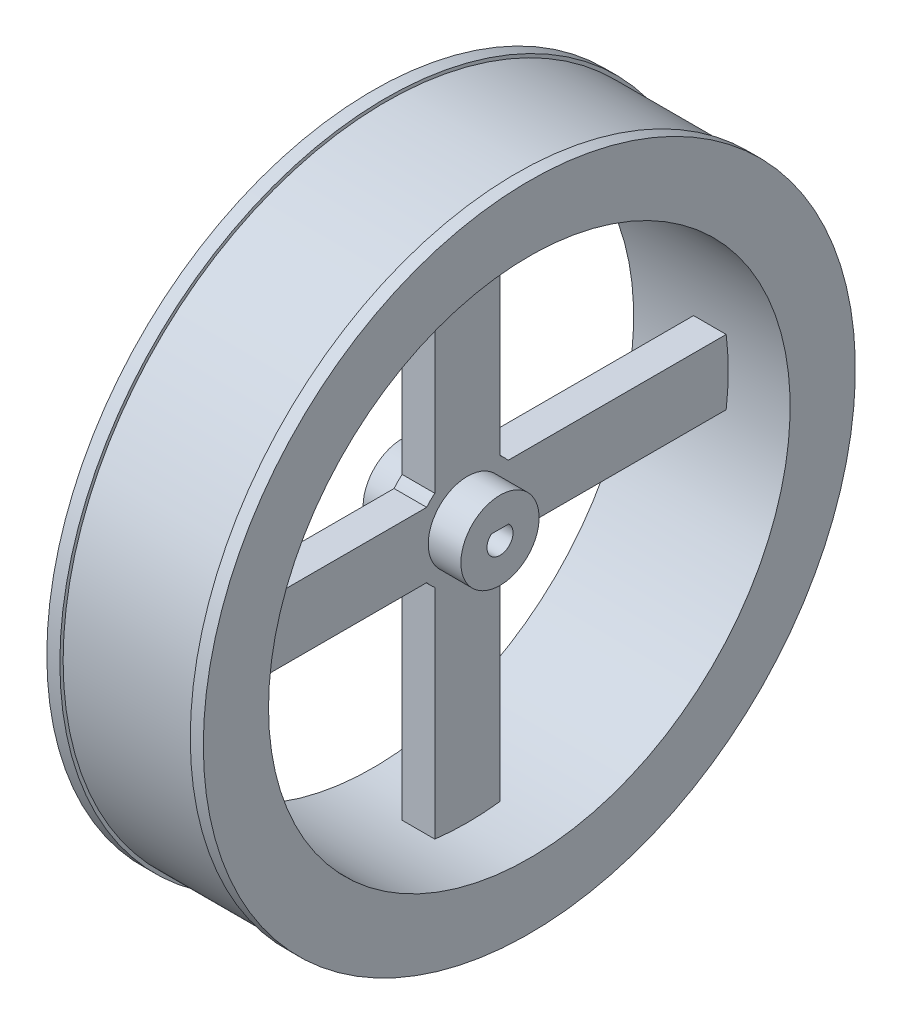
SolidWorks part; units mm, degrees
material "PLA (Black)"
ref_plane "Front Plane" through (0, 0, 0) normal (0, 0, 1) x (1, 0, 0)
ref_plane "Top Plane" through (0, 0, 0) normal (0, 1, 0) x (1, 0, 0)
ref_plane "Right Plane" through (0, 0, 0) normal (1, 0, 0) x (0, 0, -1)
sketch "Sketch1" plane through (0, 0, 0) normal (0, 0, 1) x (1, 0, 0)
  line L0 (0, 0) -> (41532.2986, 0) construction
  line L1 (-12, 50) -> (-12, 40)
  line L3 (12, 40) -> (12, 50)
  line L4 (12, 50) -> (10, 50)
  line L5 (10, 50) -> (10, 49.5)
  line L6 (10, 49.5) -> (-10, 49.5)
  line L7 (-10, 49.5) -> (-10, 50)
  line L8 (-10, 50) -> (-12, 50)
  line L9 (-12, 40) -> (12, 40)
  line L10 (7.5, 6) -> (-7.5, 6)
  line L11 (-7.5, 6) -> (-7.5, 0)
  line L12 (-7.5, 0) -> (7.5, 0)
  line L13 (7.5, 0) -> (7.5, 6)
  point P14 (0, 6)
  point P15 (0, 40)
  dimension "D1" = 100
  dimension "D2" = 0.5
  dimension "D3" = 2
  dimension "D4" = 20
  dimension "D5" = 10
  dimension "D6" = 12
  dimension "D7" = 15
revolve "Revolve1" add sketch "Sketch1" angle 360 about L0
sketch "Sketch2" plane through (0, 0, 0) normal (1, 0, 0) x (0, 0, -1)
  line L2 (0, 0) -> (0, 50000) construction
  line L9 (-5, 6.245) -> (-5, 39.6863)
  line L10 (5, 6.245) -> (5, 39.6863)
  arc A0 (-5, 39.6863) -> (5, 39.6863) centre (0, 0) cw
  arc A11 (-5, 6.245) -> (5, 6.245) centre (0, 0) ccw
  circle A12 centre (0, 0) radius 40 construction
  circle A13 centre (0, 0) radius 6
  circle A14 centre (0, 0) radius 6
  dimension "D1" = 16
  dimension "D2" = 10
  dimension "D3" = 0
extrude "Boss-Extrude1" add sketch "Sketch2" along normal mid plane 5
sketch "Sketch3" plane through (7.5, 0, 0) normal (1, 0, 0) x (0, 0, -1)
  line L0 (-1.3229, 1.5) -> (1.3229, 1.5)
  arc A0 (-1.3229, 1.5) -> (1.3229, 1.5) centre (0, 0) ccw
  dimension "D1" = 4
  dimension "D2" = 1.5
extrude "Cut-Extrude1" cut sketch "Sketch3" against normal through all both and the other way through all
pattern_circular "CirPattern1" count 4 over 360 about axis through (-12, 0, 0) along (1, 0, 0) of "Boss-Extrude1" reverse direction yes
